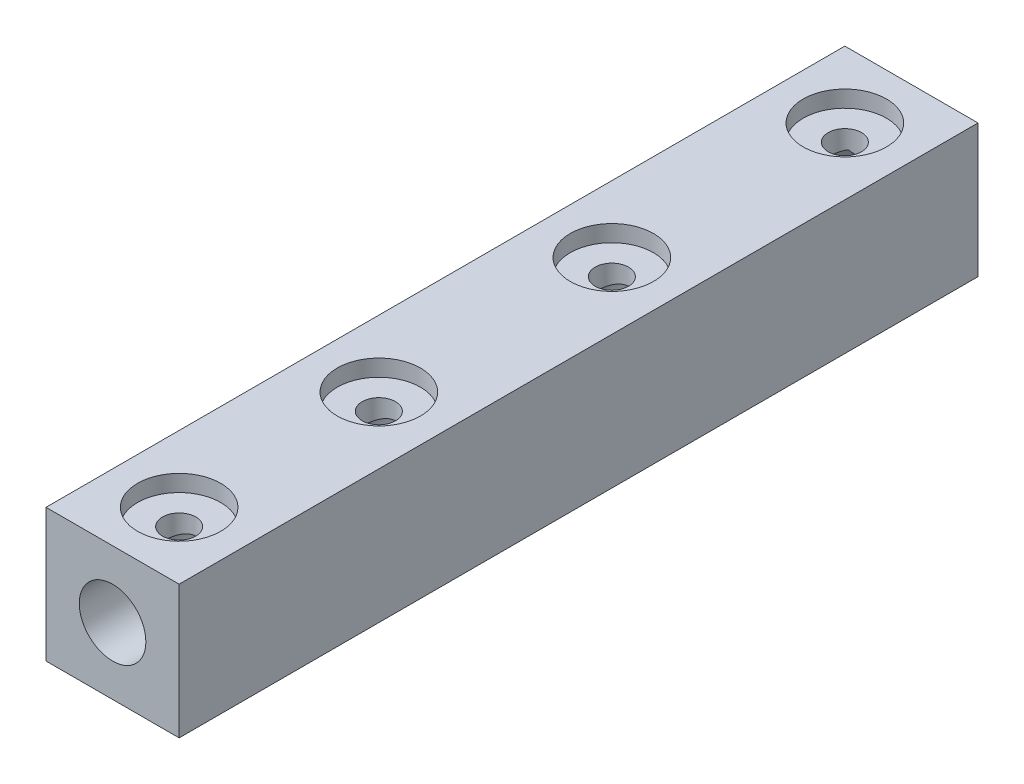
SolidWorks part; units mm, degrees
material "AISI 304"
ref_plane "Front Plane" through (0, 0, 0) normal (0, 0, 1) x (1, 0, 0)
ref_plane "Top Plane" through (0, 0, 0) normal (0, 1, 0) x (1, 0, 0)
ref_plane "Right Plane" through (0, 0, 0) normal (1, 0, 0) x (0, 0, -1)
sketch "Sketch18" plane through (0, 0, 0) normal (0, 0, 1) x (1, 0, 0)
  line L1 (12.7, 12.7) -> (-12.7, 12.7)
  line L2 (12.7, 12.7) -> (12.7, -12.7)
  line L3 (12.7, -12.7) -> (-12.7, -12.7)
  line L4 (-12.7, 12.7) -> (-12.7, -12.7)
  line L5 (12.7, 12.7) -> (-12.7, -12.7) construction
  line L6 (12.7, -12.7) -> (-12.7, 12.7) construction
  point P0 (0, 0)
  dimension "D1" = 25.4
  dimension "D2" = 25.4
extrude "Boss-Extrude3" add sketch "Sketch18" along normal mid plane 152.4
hole_wizard "1/2 (0.5) Diameter Hole2" positions "Sketch24" profile "Sketch25" hole size "1/2" standard "ANSI Inch"
sketch "Sketch24" plane through (0, 0, 76.2) normal (0, 0, 1) x (1, 0, 0)
  point P0 (0, 0)
sketch "Sketch25" plane through (0, 0, 76.2) normal (1, 0, 0) x (0, -1, 0)
  line L0 (0, 0) -> (0, 146.05)
  line L1 (0, 146.05) -> (6.35, 142.2345)
  line L2 (6.35, 142.2345) -> (6.35, 0)
  line L5 (6.35, 0) -> (0, 0)
  line L10 (0, 146.05) -> (-6.35, 142.2345) construction
  line L11 (0, -6.35) -> (0, 107.95) construction
  dimension "Hole Dia." = 12.7
  dimension "Hole Depth" = 146.05
  dimension "Drill Angle" = 118
sketch "Sketch26" plane through (0, 12.7, 0) normal (0, 1, 0) x (1, 0, 0)
  line L0 (12.7, 76.2) -> (-12.7, 76.2) construction
  line L3 (0, -63.5) -> (0, -76.2) construction
  line L4 (12.7, -76.2) -> (-12.7, -76.2) construction
  circle A0 centre (0, -63.5) radius 3.175
  circle A1 centre (0, -25.4) radius 3.175
  circle A2 centre (0, 19.05) radius 3.175
  circle A3 centre (0, 63.5) radius 3.175
  dimension "D1" = 6.35
  dimension "D2" = 12.7
  dimension "D3" = 88.9
  dimension "D4" = 12.7
  dimension "D5" = 44.45
extrude "Cut-Extrude10" cut sketch "Sketch26" against normal blind 12.7
sketch "Sketch27" plane through (0, 12.7, 0) normal (0, 1, 0) x (1, 0, 0)
  circle A0 centre (0, 63.5) radius 7.9375
  circle A1 centre (0, 19.05) radius 7.9375
  circle A2 centre (0, -25.4) radius 7.9375
  circle A3 centre (0, -63.5) radius 7.9375
  dimension "D1" = 15.875
extrude "Cut-Extrude11" cut sketch "Sketch27" against normal blind 3.175
sketch "Sketch28" plane through (0, -12.7, 0) normal (0, -1, 0) x (1, 0, 0)
  circle A0 centre (0, 25.4) radius 3.175
  circle A1 centre (0, 25.4) radius 3.175 construction
  dimension "D1" = 6.35
extrude "Cut-Extrude12" cut sketch "Sketch28" against normal blind 12.7
sketch "Sketch29" plane through (0, -12.7, 0) normal (0, -1, 0) x (-1, 0, 0)
  circle A0 centre (0, -25.4) radius 7.9375
  circle A1 centre (0, -25.4) radius 3.175 construction
  dimension "D1" = 15.875
extrude "Cut-Extrude13" cut sketch "Sketch29" against normal blind 3.175
